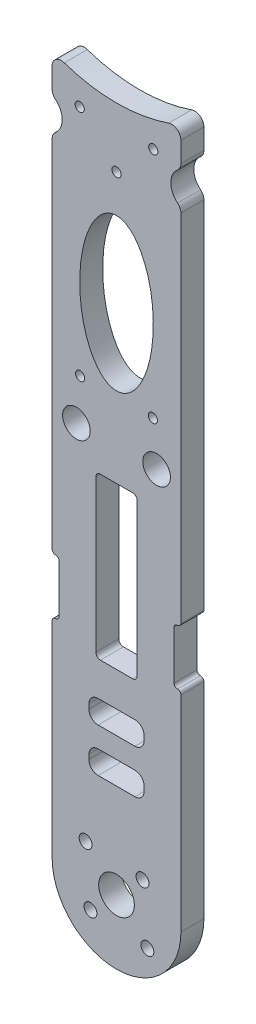
SolidWorks part; units mm, degrees
ref_plane "Front Plane" through (0, 0, 0) normal (0, 0, 1) x (1, 0, 0)
ref_plane "Top Plane" through (0, 0, 0) normal (0, 1, 0) x (1, 0, 0)
ref_plane "Right Plane" through (0, 0, 0) normal (1, 0, 0) x (0, 0, -1)
sketch "Sketch1" plane through (0, 0, 0) normal (0, 0, 1) x (1, 0, 0)
  line L0 (-14, 0) -> (-14, 44.6414)
  line L1 (0, 149.0732) -> (0, -14) construction
  line L2 (14, 0) -> (14, 44.6414)
  line L3 (-14, 0) -> (14, 0) construction
  line L4 (-6.7175, 6.7175) -> (6.7175, -6.7175) construction
  line L5 (-4, 29.9839) -> (4, 29.9839)
  line L6 (-9.9779, -9.9779) -> (8.2462, 8.2462) construction
  line L7 (-14, 144.6611) -> (-14, 149.0732)
  line L8 (-4, 20.4839) -> (4, 20.4839)
  line L9 (-6, 22.4839) -> (-6, 23.4839)
  line L10 (-4, 25.4839) -> (4, 25.4839)
  line L11 (6, 22.4839) -> (6, 23.4839)
  line L12 (-6, 20.4839) -> (6, 25.4839) construction
  line L13 (-6, 25.4839) -> (6, 20.4839) construction
  line L14 (14, 144.6611) -> (14, 149.0732)
  line L15 (-6, 31.9839) -> (-6, 32.9839)
  line L16 (-4, 34.9839) -> (4, 34.9839)
  line L17 (6, 31.9839) -> (6, 32.9839)
  line L18 (-6, 29.9839) -> (6, 34.9839) construction
  line L19 (-6, 34.9839) -> (6, 29.9839) construction
  line L21 (-3.5, 42.4439) -> (3.5, 42.4439)
  line L22 (-4.5, 43.4439) -> (-4.5, 76.4439)
  line L23 (-3.5, 77.4439) -> (3.5, 77.4439)
  line L24 (4.5, 43.4439) -> (4.5, 76.4439)
  line L25 (-4.5, 42.4439) -> (4.5, 77.4439) construction
  line L26 (-4.5, 77.4439) -> (4.5, 42.4439) construction
  line L27 (-4, 51.3814) -> (0, 51.3814) construction
  line L28 (-13.26, 57.3814) -> (-13.24, 57.3814)
  line L29 (-12.5, 56.6414) -> (-12.5, 46.1214)
  line L30 (-13.26, 45.3814) -> (-13.24, 45.3814)
  line L31 (13.26, 45.3814) -> (13.24, 45.3814)
  line L32 (12.5, 56.6414) -> (12.5, 46.1214)
  line L33 (13.26, 57.3814) -> (13.24, 57.3814)
  line L34 (14, 58.1214) -> (14, 135.3474)
  line L35 (-14, 58.1214) -> (-14, 135.3474)
  arc A0 (-14, 0) -> (14, 0) centre (0, 0) ccw
  arc A1 (-11.3514, 150.9651) -> (11.3514, 150.9651) centre (0, 184.0732) ccw
  circle A2 centre (-8, 144.3712) radius 1
  circle A3 centre (6.7175, -6.7175) radius 1.4
  circle A4 centre (-5.6569, -5.6569) radius 1.4
  circle A5 centre (5.6569, 5.6569) radius 1.4
  circle A6 centre (-6.7175, 6.7175) radius 1.4
  circle A7 centre (8, 144.3712) radius 1
  circle A8 centre (0, 136.0732) radius 1
  circle A9 centre (0, 136.0732) radius 1 construction
  circle A10 centre (-8, 144.3712) radius 1 construction
  circle A11 centre (8, 144.3712) radius 1 construction
  circle A12 centre (-7.9033, 93.7383) radius 1
  circle A13 centre (0, 184.0732) radius 35 construction
  arc A14 (6, 31.9839) -> (4, 29.9839) centre (4, 31.9839) cw
  arc A15 (4, 34.9839) -> (6, 32.9839) centre (4, 32.9839) cw
  circle A16 centre (-7.9033, 93.7383) radius 1 construction
  arc A17 (-4, 34.9839) -> (-6, 32.9839) centre (-4, 32.9839) ccw
  arc A18 (-6, 31.9839) -> (-4, 29.9839) centre (-4, 31.9839) ccw
  arc A19 (4.5, 43.4439) -> (3.5, 42.4439) centre (3.5, 43.4439) cw
  circle A20 centre (-8.7156, 84.4537) radius 3
  circle A21 centre (-8.7156, 84.4537) radius 1.45 construction
  arc A22 (6, 22.4839) -> (4, 20.4839) centre (4, 22.4839) cw
  arc A23 (4, 25.4839) -> (6, 23.4839) centre (4, 23.4839) cw
  arc A24 (-4, 25.4839) -> (-6, 23.4839) centre (-4, 23.4839) ccw
  arc A25 (-6, 22.4839) -> (-4, 20.4839) centre (-4, 22.4839) ccw
  arc A26 (-14, 149.0732) -> (-11.3514, 150.9651) centre (-12, 149.0732) cw
  arc A27 (11.3514, 150.9651) -> (14, 149.0732) centre (12, 149.0732) cw
  arc A28 (-13.2731, 143.1186) -> (-13.2731, 136.8899) centre (-15.8435, 140.0042) cw
  arc A29 (13.2731, 143.1186) -> (13.2731, 136.8899) centre (15.8435, 140.0042) ccw
  arc A30 (14, 135.3474) -> (13.2731, 136.8899) centre (12, 135.3474) ccw
  arc A31 (13.2731, 143.1186) -> (14, 144.6611) centre (12, 144.6611) ccw
  arc A32 (-14, 144.6611) -> (-13.2731, 143.1186) centre (-12, 144.6611) ccw
  arc A33 (-13.2731, 136.8899) -> (-14, 135.3474) centre (-12, 135.3474) ccw
  circle A34 centre (7.9033, 93.7383) radius 1
  circle A35 centre (8.7156, 84.4537) radius 3
  arc A36 (-3.5, 42.4439) -> (-4.5, 43.4439) centre (-3.5, 43.4439) cw
  arc A37 (-4.5, 76.4439) -> (-3.5, 77.4439) centre (-3.5, 76.4439) cw
  arc A38 (3.5, 77.4439) -> (4.5, 76.4439) centre (3.5, 76.4439) cw
  arc A39 (-14, 44.6414) -> (-13.26, 45.3814) centre (-13.26, 44.6414) cw
  arc A40 (-13.24, 45.3814) -> (-12.5, 46.1214) centre (-13.24, 46.1214) ccw
  arc A41 (-12.5, 56.6414) -> (-13.24, 57.3814) centre (-13.24, 56.6414) ccw
  arc A42 (-13.26, 57.3814) -> (-14, 58.1214) centre (-13.26, 58.1214) cw
  arc A43 (12.5, 46.1214) -> (13.24, 45.3814) centre (13.24, 46.1214) ccw
  arc A44 (13.26, 45.3814) -> (14, 44.6414) centre (13.26, 44.6414) cw
  arc A45 (13.24, 57.3814) -> (12.5, 56.6414) centre (13.24, 56.6414) ccw
  arc A46 (13.26, 57.3814) -> (14, 58.1214) centre (13.26, 58.1214) ccw
  ellipse E1 centre (0, 111.3839) end of major axis (0, 127.8839) minor radius 8
  point P33 (0, 32.4839)
  point P43 (0, 22.9839)
  point P82 (-14, 151.9952)
  point P85 (14, 151.9952)
  point P94 (14, 136.4115)
  point P97 (14, 143.597)
  point P100 (-14, 143.597)
  point P103 (-14, 136.4115)
  point P109 (0, 59.9439)
  point P135 (-12.5, 51.3814)
  point P141 (-14, 45.3814)
  point P144 (-12.5, 45.3814)
  point P147 (-12.5, 57.3814)
  point P150 (-14, 57.3814)
  point P153 (12.5, 45.3814)
  point P156 (14, 45.3814)
  point P159 (12.5, 57.3814)
  point P162 (14, 57.3814)
  dimension "D3" = 14
  dimension "D5" = 2
  dimension "D2" = 2
  dimension "D4" = 12
  dimension "D8" = 35
  dimension "D10" = 9
  dimension "D11" = 9.5
  dimension "D7" = 2
  dimension "D15" = 2
  dimension "D16" = 2
  dimension "D18" = 2.8
  dimension "D19" = 9.5
  dimension "D20" = 8
  dimension "D14" = 1
  dimension "D24" = 0.74
  dimension "D6" = 5
  dimension "D9" = 4.5
  dimension "D12" = 35
  dimension "D13" = 8
  dimension "D17" = 8
  dimension "D21" = 1.5
  dimension "D22" = 163.0732
  dimension "D23" = 6
extrude "Boss-Extrude1" add sketch "Sketch1" along normal blind 5
sketch "Sketch2" plane through (0, 0, 5) normal (0, 0, 1) x (1, 0, 0)
  circle A0 centre (0, 0) radius 3.875
extrude "Cut-Extrude1" cut sketch "Sketch2" against normal up to next
